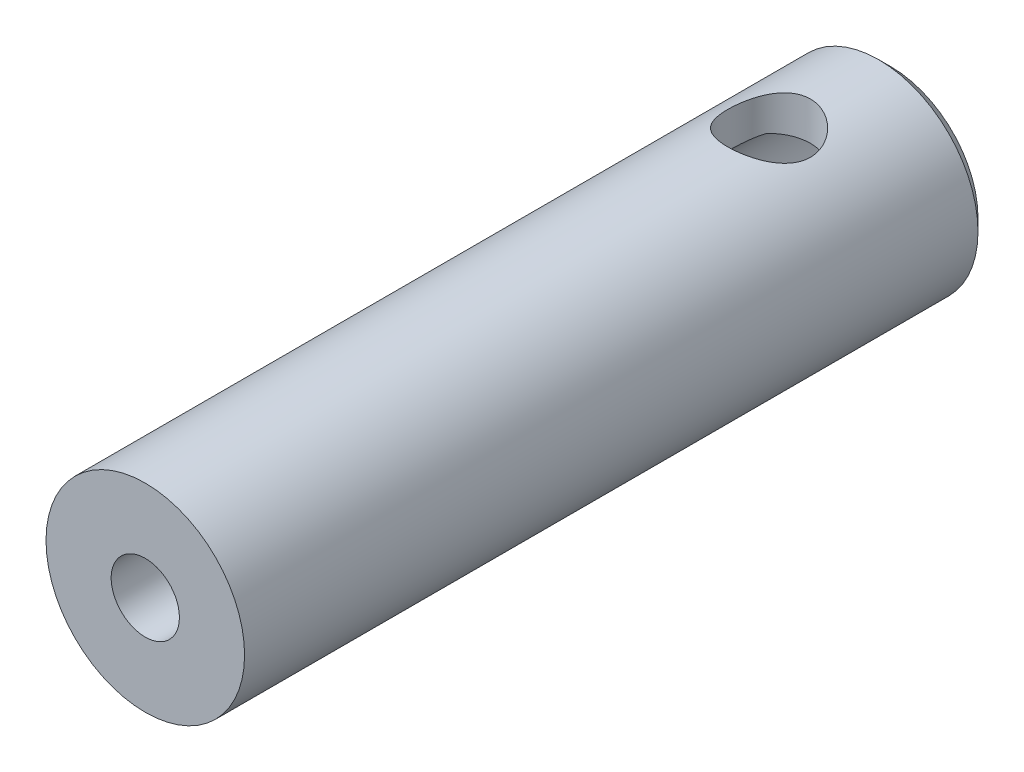
SolidWorks part; units mm, degrees
material "3.0205 (EN-AW 1200)"
ref_plane "Plan de face" through (0, 0, 0) normal (0, 0, 1) x (1, 0, 0)
ref_plane "Plan de dessus" through (0, 0, 0) normal (0, 1, 0) x (1, 0, 0)
ref_plane "Plan de droite" through (0, 0, 0) normal (1, 0, 0) x (0, 0, -1)
sketch "Esquisse1" plane through (0, 0, 0) normal (0, 0, 1) x (1, 0, 0)
  circle A0 centre (0, 0) radius 4.075
  dimension "D1" = 8.15
extrude "Boss.-Extru.1" add sketch "Esquisse1" along normal blind 30.6
sketch "Esquisse2" plane through (0, 0, 0) normal (0, 0, -1) x (-1, 0, 0)
  line L0 (-1.261, 2.5) -> (1.261, 2.5)
  arc A0 (-1.261, 2.5) -> (1.261, 2.5) centre (0, 0) ccw
  dimension "D1" = 2.8
  dimension "D2" = 2.5
extrude "Enlèv. mat.-Extru.1" cut sketch "Esquisse2" against normal blind 14
sketch "Esquisse3" plane through (0, 0, 0) normal (0, 0, -1) x (-1, 0, 0)
  circle A0 centre (0, 0) radius 2.8
extrude "Enlèv. mat.-Extru.2" cut sketch "Esquisse3" against normal blind 3
chamfer "Chanfrein1" distance 0.5 angle 45 1 edges at (4.075, 0, 0)
sketch "Esquisse5" plane through (0, 0, 30.6) normal (0, 0, 1) x (1, 0, 0)
  circle A0 centre (0, 0) radius 1.4
  dimension "D1" = 2.8
extrude "Enlèv. mat.-Extru.4" cut sketch "Esquisse5" against normal blind 10
ref_plane "Plan1" through (0, 4.075, 0) normal (0, 1, 0) x (1, 0, 0)
sketch "Esquisse7" plane through (0, 4.075, 0) normal (0, 1, 0) x (1, 0, 0)
  line L0 (0, 0) -> (0, -5) construction
  point P4 (0, -5)
  dimension "D1" = 5
hole_wizard "Dégagement M31" positions "Esquisse8" profile "Esquisse9" hole size "M3" standard "ISO"
sketch "Esquisse8" plane through (0, 4.075, 0) normal (0, 1, 0) x (1, 0, 0)
  point P0 (0, -5)
sketch "Esquisse9" plane through (0, 4.075, 5) normal (1, 0, 0) x (0, 0, 1)
  line L0 (0, 0) -> (0, 5.0215)
  line L1 (0, 5.0215) -> (1.7, 4)
  line L2 (1.7, 4) -> (1.7, 0)
  line L5 (1.7, 0) -> (0, 0)
  line L10 (0, 5.0215) -> (-1.7, 4) construction
  line L11 (0, -6.35) -> (0, 107.95) construction
  dimension "Diamètre du perçage" = 3.4
  dimension "Profondeur du perçage" = 4
  dimension "Angle de pointe" = 118
sketch "Esquisse10" plane through (0, 0, 0) normal (0, 1, 0) x (1, 0, 0)
  line L0 (4.5892, -26.4508) -> (0, -22.6) construction
  line L2 (0, -22.6) -> (0, -30.6) construction
  line L3 (-4.075, -30.6) -> (4.075, -30.6) construction
  line L4 (2.4223, -23.5882) -> (1.9081, -24.2011)
  line L5 (2.4223, -23.5882) -> (5.1035, -25.838)
  line L7 (1.9081, -24.2011) -> (4.5892, -26.4508)
  line L8 (4.5892, -26.4508) -> (4.075, -27.0637) construction
  line L9 (4.075, -27.0637) -> (1.3938, -24.8139) construction
  line L10 (1.3938, -24.8139) -> (1.9081, -24.2011) construction
  line L11 (4.075, -30.6) -> (4.075, -27.0637) construction
  line L12 (4.5892, -26.4508) -> (5.1035, -25.838)
  dimension "D1" = 0.8
  dimension "D2" = 50
  dimension "D3" = 8
  dimension "D4" = 3.5
revolve "Enlèvement de matière-Révolution1" [suppressed] cut sketch "Esquisse10" angle 360 about L7
pattern_circular "Répétition circulaire1" [suppressed] count 3 over 360 of bodies 108
